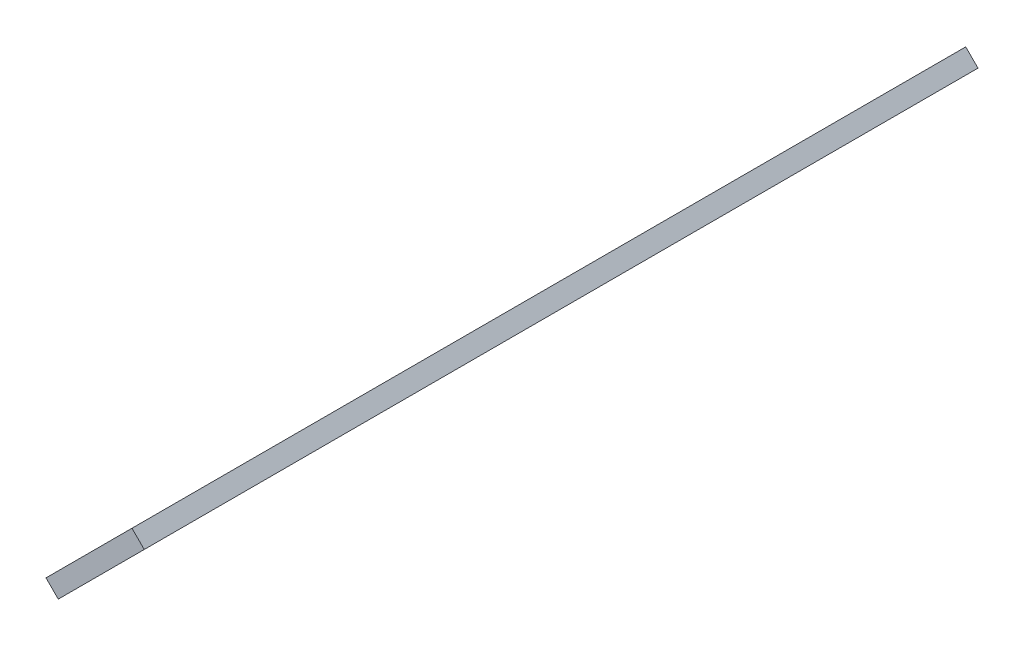
SolidWorks part; units mm, degrees
ref_plane "Front Plane" through (0, 0, 0) normal (0, 0, 1) x (1, 0, 0)
ref_plane "Top Plane" through (0, 0, 0) normal (0, 1, 0) x (1, 0, 0)
ref_plane "Right Plane" through (0, 0, 0) normal (1, 0, 0) x (0, 0, -1)
sketch "Sketch1" plane through (0, 0, 0) normal (0, 0, 1) x (1, 0, 0)
  line L0 (91.6648, 29.3027) -> (52.5461, -9.816) construction
  line L2 (78.5772, 20.7053) -> (74.1015, 16.2295) construction
  line L3 (78.5917, 11.7394) -> (83.0674, 16.2151) construction
  line L4 (39.9621, 9.9289) -> (35.472, 14.4191)
  line L5 (39.9621, 9.9289) -> (71.393, 41.3598)
  line L6 (35.472, 14.4191) -> (66.9029, 45.85)
  line L7 (71.393, 41.3598) -> (66.9029, 45.85)
  line L8 (108.2121, 4.5408) -> (76.7812, -26.8901) construction
  line L9 (76.7812, -26.8901) -> (72.2911, -22.4) construction
  line L10 (103.722, 9.0309) -> (72.2911, -22.4) construction
extrude "Boss-Extrude1" add sketch "Sketch1" along normal up to surface (304.8 mm away)
